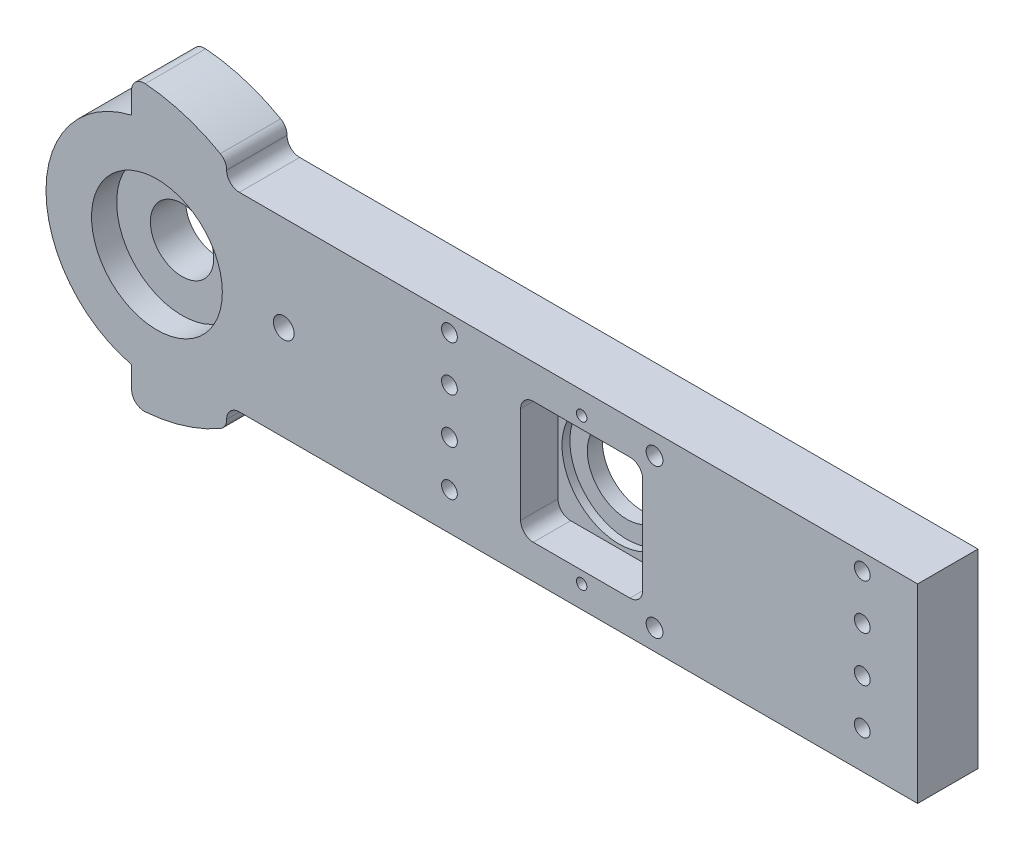
SolidWorks part; units mm, degrees
material "PE High Density"
ref_plane "Front Plane" through (0, 0, 0) normal (0, 0, 1) x (1, 0, 0)
ref_plane "Top Plane" through (0, 0, 0) normal (0, 1, 0) x (1, 0, 0)
ref_plane "Right Plane" through (0, 0, 0) normal (1, 0, 0) x (0, 0, -1)
sketch "Sketch1" plane through (0, 0, 0) normal (0, 0, 1) x (1, 0, 0)
  line L0 (30, 0) -> (30, 30) construction
  line L3 (0, 30) -> (18.0278, 30) construction
  line L6 (0, 0) -> (30, 0) construction
  line L8 (18.0278, 30) -> (240, 30)
  line L9 (240, 30) -> (240, -30)
  line L11 (18.0278, -30) -> (240, -30)
  circle A0 centre (0, 0) radius 30 construction
  arc A2 (18.0278, 30) -> (18.0278, -30) centre (0, 0) ccw
  circle A5 centre (0, 0) radius 10
  dimension "D1" = 60
  dimension "D4" = 70
  dimension "D8" = 20
  dimension "D2" = 240
extrude "Boss-Extrude1" add sketch "Sketch1" along normal mid plane 19.05
sketch "Sketch2" plane through (0, 0, -9.525) normal (0, 0, 1) x (1, 0, 0)
  line L0 (240, -30) -> (240, 30) construction
  circle A0 centre (134, 0) radius 12.5
  dimension "D2" = 25
  dimension "D1" = 106
extrude "Cut-Extrude1" cut sketch "Sketch2" along normal through all
sketch "Sketch3" plane through (0, 0, 9.525) normal (0, 0, 1) x (1, 0, 0)
  line L1 (114.5, -19.5) -> (153.5, -19.5) construction
  line L2 (114.5, -19.5) -> (114.5, 19.5) construction
  line L3 (114.5, 19.5) -> (153.5, 19.5) construction
  line L4 (153.5, -19.5) -> (153.5, 19.5) construction
  line L5 (114.5, -19.5) -> (153.5, 19.5) construction
  line L6 (114.5, 19.5) -> (153.5, -19.5) construction
  circle A0 centre (134, 0) radius 12.5 construction
  circle A3 centre (134, 0) radius 18
  dimension "D1" = 36
  dimension "D2" = 39
  dimension "D3" = 39
extrude "Cut-Extrude2" cut sketch "Sketch3" against normal blind 14.2875
sketch "Sketch4" plane through (0, 0, 9.525) normal (0, 0, 1) x (1, 0, 0)
  circle A0 centre (0, 0) radius 20.6375
  dimension "D1" = 41.275
extrude "Cut-Extrude3" cut sketch "Sketch4" against normal blind 7.9375
sketch "Sketch5" plane through (0, 0, 9.525) normal (0, 0, 1) x (1, 0, 0)
  line L1 (114.75, -19.25) -> (153.25, -19.25)
  line L2 (114.75, -19.25) -> (114.75, 19.25)
  line L3 (114.75, 19.25) -> (153.25, 19.25)
  line L4 (153.25, -19.25) -> (153.25, 19.25)
  line L5 (114.75, -19.25) -> (153.25, 19.25) construction
  line L6 (114.75, 19.25) -> (153.25, -19.25) construction
  point P0 (134, 0)
  dimension "D1" = 38.5
  dimension "D2" = 38.5
extrude "Cut-Extrude4" cut sketch "Sketch5" against normal offset from surface (11.7875 mm away) 2.5 up to face at (146.5, 0, -4.7625)
fillet "Fillet3" radius 4 4 edges at (153.25, -19.25, 3.6313) (114.75, -19.25, 3.6313) (153.25, 19.25, 3.6313) (114.75, 19.25, 3.6313)
sketch "Sketch12" plane through (0, 0, 9.525) normal (0, 0, 1) x (1, 0, 0)
  line L1 (240, 30) -> (18.0278, 30) construction
  line L3 (22, 30) -> (22, 36.35)
  line L4 (-8, 45) -> (22, 45) construction
  line L5 (-8, 45) -> (-8, 34.0735)
  line L6 (240, 30) -> (18.0278, 30) construction
  line L7 (22, 30) -> (18.0278, 30)
  arc A0 (-8, 45) -> (22, 36.35) centre (-8, -11.3481) cw
  arc A1 (18.0278, 30) -> (18.0278, -30) centre (0, 0) ccw construction
  arc A2 (18.0278, 30) -> (-8, 34.0735) centre (0, 0) ccw
  dimension "D2" = 6.35
  dimension "D3" = 30
  dimension "D1" = 45
  dimension "D4" = 8
extrude "Boss-Extrude2" add sketch "Sketch12" against normal through all
mirror "Mirror4" about plane through (0, 0, 0) normal (0, 1, 0) of "Boss-Extrude2"
fillet "Fillet4" radius 4 4 edges at (22, 36.35, 0) (22, -36.35, 0) (-8, -45, 0) (-8, 45, 0)
fillet "Fillet6" radius 4 2 edges at (22, 30, 0) (22, -30, 0)
sketch "Sketch14" plane through (0, 0, 9.525) normal (0, 0, 1) x (1, 0, 0)
  line L0 (0, 0) -> (40, 0) construction
  line L1 (0, 0) -> (40, 0) construction
  circle A0 centre (0, 0) radius 40 construction
  circle A1 centre (40, 0) radius 3.2639
  dimension "D1" = 80
  dimension "D2" = 6.5278
  dimension "D3" = 0
extrude "Cut-Extrude6" cut sketch "Sketch14" against normal through all
sketch "Sketch15" plane through (0, 0, 9.525) normal (0, 0, 1) x (1, 0, 0)
  line L0 (134, 0) -> (134, 23) construction
  line L1 (240, 30) -> (26, 30) construction
  line L2 (134, 0) -> (146.5, 0) construction
  circle A0 centre (134, 0) radius 12.5 construction
  point P0 (134, 23)
  point P9 (134, -23)
  dimension "D1" = 7
hole_wizard "M4x0.7 Tapped Hole1" positions "Sketch16" profile "Sketch17" tap size "M4x0.7" standard "ANSI Metric" end condition through all
sketch "Sketch16" plane through (0, 0, -9.525) normal (0, 0, -1) x (-1, 0, 0)
  point P0 (-134, 23)
  point P3 (-134, -23)
sketch "Sketch17" plane through (134, 23, -9.525) normal (1, 0, 0) x (0, 1, 0)
  line L0 (0, 0) -> (0, 19.05)
  line L1 (0, 19.05) -> (1.65, 19.05)
  line L2 (1.65, 19.05) -> (1.65, 0)
  line L5 (1.65, 0) -> (0, 0)
  line L11 (0, -6.35) -> (0, 107.95) construction
  dimension "Thru Tap Drill Dia." = 3.3
  dimension "Thru Tap Drill Depth" = 19.05
cosmetic thread "Hole Thread1" parameters "D2"=4
cosmetic thread "Hole Thread2" parameters "D2"=4
sketch "Sketch18" plane through (0, 0, 9.525) normal (0, 0, 1) x (1, 0, 0)
  line L0 (26, -30) -> (240, -30) construction
  line L1 (240, 30) -> (227.3, 30) construction
  line L2 (240, 30) -> (240, -30) construction
  line L3 (240, -30) -> (227.3, -30) construction
  line L4 (227.3, 30) -> (227.3, -30) construction
  line L5 (240, 30) -> (26, 30) construction
  line L6 (97.05, 30) -> (109.75, 30) construction
  line L7 (97.05, 30) -> (97.05, -30) construction
  line L8 (97.05, -30) -> (109.75, -30) construction
  line L9 (109.75, 30) -> (109.75, -30) construction
  line L10 (222.5375, 30) -> (222.5375, -30) construction
  line L11 (97.05, 30) -> (87.525, 30) construction
  line L12 (97.05, 30) -> (97.05, -30) construction
  line L13 (97.05, -30) -> (87.525, -30) construction
  line L14 (87.525, 30) -> (87.525, -30) construction
  line L15 (227.3, 30) -> (217.775, 30) construction
  line L16 (227.3, 30) -> (227.3, -30) construction
  line L17 (227.3, -30) -> (217.775, -30) construction
  line L18 (217.775, 30) -> (217.775, -30) construction
  line L19 (92.2875, 30) -> (92.2875, -30) construction
  line L20 (222.5375, -18.0938) -> (222.5375, -3.8063) construction
  point P21 (92.2875, -18.0938)
  point P22 (222.5375, -18.0938)
  point P24 (92.2875, -3.8063)
  point P25 (222.5375, -3.8063)
  point P26 (92.2875, 10.4812)
  point P27 (222.5375, 10.4812)
  point P28 (92.2875, 24.7687)
  point P29 (222.5375, 24.7687)
  dimension "D1" = 12.7
  dimension "D2" = 12.7
  dimension "D3" = 130.25
  dimension "D4" = 9.525
  dimension "D5" = 9.525
  dimension "D6" = 11.9062
  dimension "D8" = 14.2875
  dimension "D7" = 4
hole_wizard "CSK for #10 Flat Head Machine Screw1" positions "Sketch19" profile "Sketch20" countersink size "#10" standard "ANSI Inch" end condition up to next
sketch "Sketch19" plane through (0, 0, -9.525) normal (0, 0, -1) x (-1, 0, 0)
  point P0 (-92.2875, 24.7687)
  point P3 (-92.2875, 10.4812)
  point P6 (-92.2875, -3.8063)
  point P9 (-92.2875, -18.0938)
  point P12 (-222.5375, 24.7687)
  point P15 (-222.5375, 10.4812)
  point P18 (-222.5375, -3.8063)
  point P21 (-222.5375, -18.0938)
sketch "Sketch20" plane through (92.2875, 24.7687, -9.525) normal (1, 0, 0) x (0, 1, 0)
  line L0 (0, 0) -> (0, 19.05)
  line L1 (0, 19.05) -> (2.4892, 19.05)
  line L2 (2.4892, 19.05) -> (2.4892, 3.1265)
  line L3 (2.4892, 3.1265) -> (5.207, 0)
  line L5 (5.207, 0) -> (0, 0)
  line L6 (-2.4892, 3.1265) -> (-5.207, 0) construction
  line L11 (0, -6.35) -> (0, 107.95) construction
  dimension "Thru Hole Dia." = 4.9784
  dimension "Thru Hole Depth" = 19.05
  dimension "Near C'Sink Dia." = 10.414
  dimension "Near C'Sink Angle" = 82
sketch "Sketch21" plane through (0, 0, -9.525) normal (0, 0, -1) x (-1, 0, 0)
  line L0 (-240, -30) -> (-240, 30) construction
  line L1 (-240, 30) -> (-26, 30) construction
  line L2 (0, 0) -> (35, 0) construction
  arc A0 (8, -34.0735) -> (8, 34.0735) centre (0, 0) ccw construction
  point P0 (-157, 23.5)
  point P11 (-157, -23.5)
  dimension "D1" = 83
  dimension "D2" = 6.5
hole_wizard "CSK for M5 Flat Head Machine Screw1" positions "Sketch22" profile "Sketch23" countersink size "M5" standard "ANSI Metric" end condition through all
sketch "Sketch22" plane through (0, 0, -9.525) normal (0, 0, -1) x (-1, 0, 0)
  point P0 (-157, 23.5)
  point P3 (-157, -23.5)
sketch "Sketch23" plane through (157, 23.5, -9.525) normal (1, 0, 0) x (0, 1, 0)
  line L0 (0, 0) -> (0, 19.05)
  line L1 (0, 19.05) -> (2.65, 19.05)
  line L2 (2.65, 19.05) -> (2.65, 2.6)
  line L3 (2.65, 2.6) -> (5.25, 0)
  line L5 (5.25, 0) -> (0, 0)
  line L6 (-2.65, 2.6) -> (-5.25, 0) construction
  line L11 (0, -6.35) -> (0, 107.95) construction
  dimension "Thru Hole Dia." = 5.3
  dimension "Thru Hole Depth" = 19.05
  dimension "Near C'Sink Dia." = 10.5
  dimension "Near C'Sink Angle" = 90
equation "\"D1@Boss-Extrude1\"=0.75in"
equation "\"D1@Sketch4\"=1.625in"
equation "\"D1@Sketch1\"=60"
equation "\"D1@Cut-Extrude2\"=8.000000mm+6.2875"
equation "\"D2@Sketch12\"=0.25in"
equation "\"D2@Sketch14\"=0.257in"
equation "\"D1@Sketch18\"=0.5in"
equation "\"D2@Sketch18\"=0.5in"
equation "\"D4@Sketch18\"=0.375in"
equation "\"D5@Sketch18\"=0.375in"
equation "\"D6@Sketch18\"=0.1875in + 0.5625in / 2"
